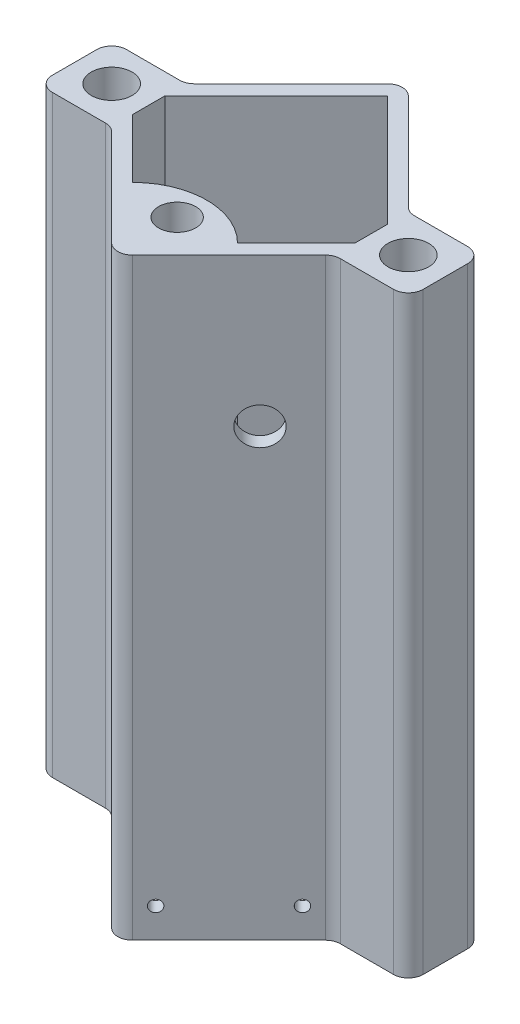
SolidWorks part; units mm, degrees
ref_plane "Front Plane" through (0, 0, 0) normal (0, 0, 1) x (1, 0, 0)
ref_plane "Top Plane" through (0, 0, 0) normal (0, 1, 0) x (1, 0, 0)
ref_plane "Right Plane" through (0, 0, 0) normal (1, 0, 0) x (0, 0, -1)
sketch "Sketch2" plane through (0, 0, 0) normal (0, 1, 0) x (1, 0, 0)
  line L32 (-25.4, 0) -> (-19.05, 0) construction
  line L33 (-25.4, 0) -> (0, 25.4)
  line L34 (-19.05, -6.35) -> (-31.75, -6.35)
  line L35 (-19.05, -6.35) -> (-19.05, 6.35)
  line L36 (-19.05, 6.35) -> (-31.75, 6.35)
  line L37 (-31.75, -6.35) -> (-31.75, 6.35)
  line L38 (-19.05, -6.35) -> (-31.75, 6.35) construction
  line L39 (-19.05, 6.35) -> (-31.75, -6.35) construction
  line L40 (19.05, -6.35) -> (31.75, -6.35)
  line L41 (19.05, -6.35) -> (19.05, 6.35)
  line L42 (19.05, 6.35) -> (31.75, 6.35)
  line L43 (31.75, -6.35) -> (31.75, 6.35)
  line L44 (19.05, -6.35) -> (31.75, 6.35) construction
  line L45 (19.05, 6.35) -> (31.75, -6.35) construction
  line L46 (0, -55) -> (0, 55) construction
  line L47 (0, 25.4) -> (25.4, 0)
  line L48 (25.4, 0) -> (0, -25.4)
  line L49 (0, -25.4) -> (-25.4, 0)
  line L50 (-19.05, 2.7579) -> (0, 21.8079)
  line L51 (19.05, 0) -> (25.4, 0) construction
  line L52 (0, 21.8079) -> (19.05, 2.7579)
  line L53 (19.05, -2.7579) -> (0, -21.8079)
  line L54 (0, -21.8079) -> (-19.05, -2.7579)
  line L55 (-21.8079, 0) -> (0, 21.8079) construction
  line L56 (0, -21.8079) -> (-21.8079, 0) construction
  line L57 (0, 21.8079) -> (21.8079, 0) construction
  line L58 (21.8079, 0) -> (0, -21.8079) construction
  circle A0 centre (25.4, 0) radius 3.4925
  circle A1 centre (-25.4, 0) radius 3.4925
  point P0 (0, 0)
  point P5 (0, 0)
  point P6 (0, 23.4835)
  point P8 (0, 22.9275)
  dimension "D1" = 50.8
  dimension "D2" = 6.35
  dimension "D4" = 6.985
  dimension "D3" = 2.54
  dimension "D5" = 50.8
  dimension "D6" = 12.7
extrude "Boss-Extrude1" add sketch "Sketch2" along normal blind 101.6 contours L42 L36 | L40 L34 | L50 L52 L41 L47 L33 L35 | A1 L49 L35 L33 | A1 L33 L36 L37 L34 L49 | L53 L54 L35 L49 L48 L41 | A0 L47 L41 L48 | A0 L48 L40 L43 L42 L47 region at (-20.5007, 0, 0) region at (-9.2116, 0, -15.5616) region at (-21.1172, 0, -4.5368) region at (20.5007, 0, 0) region at (25.4, 0, -6.1704) region at (-9.8384, 0, 12.5963)
fillet "Fillet1" radius 2.54 10 edges at (-31.75, 50.8, -6.35) (-31.75, 50.8, 6.35) (31.75, 50.8, 6.35) (31.75, 50.8, -6.35) (-19.05, 50.8, 6.35) (0, 50.8, 25.4) (19.05, 50.8, 6.35) (19.05, 50.8, -6.35) (0, 50.8, -25.4) (-19.05, 50.8, -6.35)
sketch "Sketch11" plane through (12.7, 0, -12.7) normal (0.7071, 0, -0.7071) x (-0.7071, 0, -0.7071)
  line L0 (-5.1438, 5.08) -> (12.6362, 5.08) construction
  line L1 (15.4205, 0) -> (-7.9282, 0) construction
  circle A0 centre (-5.1438, 5.08) radius 1
  circle A1 centre (12.6362, 5.08) radius 1
  point P6 (3.7462, 0)
  point P7 (3.7462, 5.08)
  dimension "D2" = 2
  dimension "D1" = 17.78
  dimension "D3" = 5.08
extrude "Cut-Extrude1" cut sketch "Sketch11" against normal up to surface (2.54 mm away) and the other way through all up to face at (9.525, 50.8, -12.2829)
mirror "Mirror2" about plane through (0, 0, 0) normal (1, 0, 0) of "Cut-Extrude1"
mirror "Mirror3" about plane through (0, 0, 0) normal (0, 0, 1) of "Mirror2", "Cut-Extrude1"
ref_axis "Axis2" through (0, -5.08, 0) along (0, 1, 0)
sketch "Sketch12" plane through (-12.7, 0, -12.7) normal (-0.7071, 0, -0.7071) x (-0.7071, 0, 0.7071)
  line L1 (7.9282, 101.6) -> (-15.4205, 101.6) construction
  line L2 (0, -5.08) -> (0, 106.68) construction
  circle A0 centre (0, 76.2) radius 3.175
  point P2 (0, 0)
  point P3 (0, 0)
  point P7 (0, 0)
  dimension "D1" = 6.35
  dimension "D2" = 25.4
extrude "Cut-Extrude2" cut sketch "Sketch12" against normal through all both and the other way through all
sketch "Sketch13" plane through (12.7, 0, -12.7) normal (0.7071, 0, -0.7071) x (-0.7071, 0, -0.7071)
  line L0 (0, -5.08) -> (0, 106.68) construction
  line L1 (15.4205, 101.6) -> (-7.9282, 101.6) construction
  circle A0 centre (0, 63.5) radius 3.175
  point P4 (0, 0)
  dimension "D1" = 6.35
  dimension "D2" = 38.1
extrude "Cut-Extrude3" cut sketch "Sketch13" against normal through all both and the other way through all
sketch "Sketch14" plane through (0, 101.6, 0) normal (0, 1, 0) x (1, 0, 0)
  line L0 (19.05, -2.7579) -> (0, -21.8079) construction
  line L1 (0, -21.8079) -> (-19.05, -2.7579) construction
  line L2 (8.9803, -12.8276) -> (0, -21.8079)
  line L3 (0, -21.8079) -> (-8.9803, -12.8276)
  arc A0 (8.9803, -12.8276) -> (-8.9803, -12.8276) centre (0, -21.8079) ccw
  circle A1 centre (0, -14.1879) radius 3.175
  point P6 (0, 0)
  dimension "D1" = 25.4
  dimension "D2" = 6.35
  dimension "D3" = 7.62
extrude "Boss-Extrude2" add sketch "Sketch14" against normal blind 76.2
